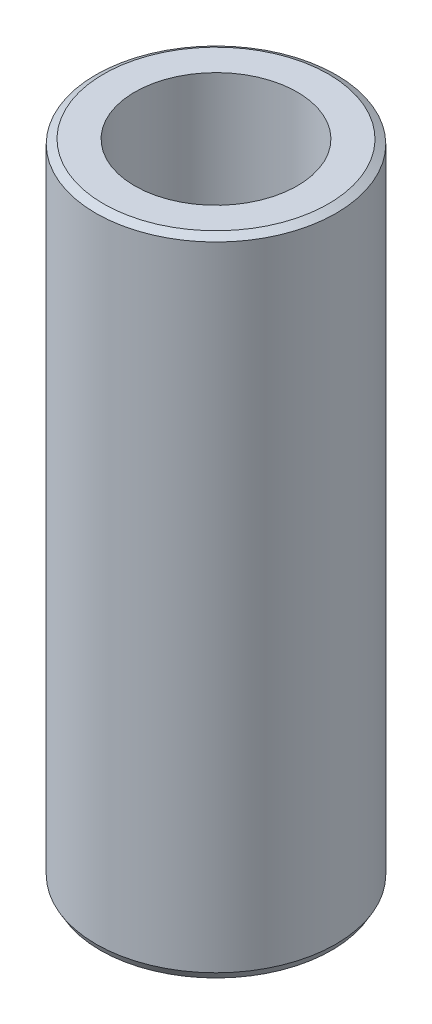
SolidWorks part; units mm, degrees
ref_plane "Front Plane" through (0, 0, 0) normal (0, 0, 1) x (1, 0, 0)
ref_plane "Top Plane" through (0, 0, 0) normal (0, 1, 0) x (1, 0, 0)
ref_plane "Right Plane" through (0, 0, 0) normal (1, 0, 0) x (0, 0, -1)
sketch "Sketch1" plane through (0, 0, 0) normal (0, 1, 0) x (1, 0, 0)
  circle A0 centre (0, 0) radius 60
  dimension "SHAFT_OD" = 120
extrude "Boss-Extrude1" add sketch "Sketch1" along normal blind 322.279
sketch "Sketch2" plane through (0, 0, 0) normal (0, 1, 0) x (1, 0, 0)
  circle A0 centre (0, 0) radius 40.6279
  dimension "BORE_D" = 81.2558
extrude "Cut-Extrude1" cut sketch "Sketch2" along normal through all
chamfer "Chamfer1" distance 2.194 angle 60 2 edges at (0, 322.279, 60) (0, 0, 60) first distance on face at (0, 322.279, 60) first distance on face at (0, 0, 40.6279)
